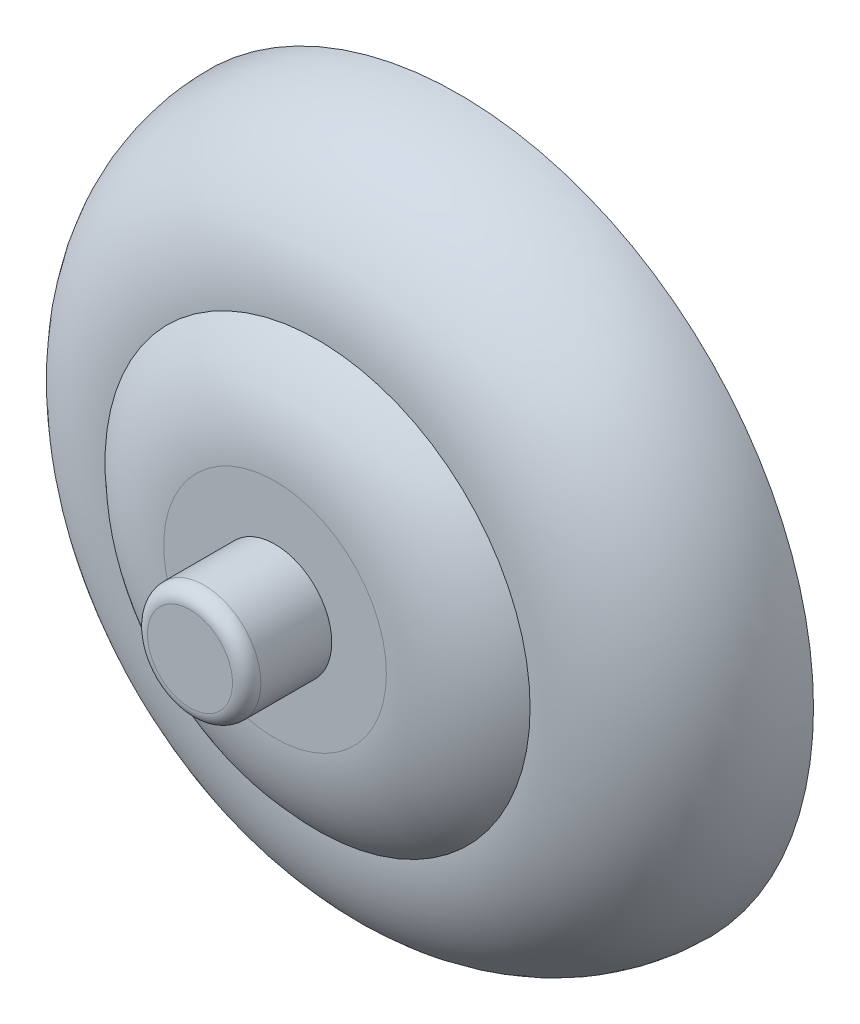
SolidWorks part; units mm, degrees
ref_plane "Plan de face" through (0, 0, 0) normal (0, 0, 1) x (1, 0, 0)
ref_plane "Plan de dessus" through (0, 0, 0) normal (0, 1, 0) x (1, 0, 0)
ref_plane "Plan de droite" through (0, 0, 0) normal (1, 0, 0) x (0, 0, -1)
sketch "Esquisse1" plane through (0, 0, 0) normal (0, 0, 1) x (1, 0, 0)
  circle A0 centre (0, 0) radius 25
  dimension "D1" = 50
extrude "Boss.-Extru.1" add sketch "Esquisse1" along normal blind 10
sketch "Esquisse2" plane through (0, 0, 10) normal (0, 0, 1) x (1, 0, 0)
  circle A0 centre (0, 0) radius 15
  dimension "D1" = 30
extrude "Boss.-Extru.2" add sketch "Esquisse2" along normal blind 3
sketch "Esquisse3" plane through (0, 0, 13) normal (0, 0, 1) x (1, 0, 0)
  circle A0 centre (0, 0) radius 4
  dimension "D1" = 8
extrude "Boss.-Extru.3" add sketch "Esquisse3" along normal blind 6
fillet "Congé1" radius 10 1 edges at (15, 0, 13)
fillet "Congé2" radius 1 1 edges at (4, 0, 19)
fillet "Congé3" radius 10 1 edges at (25, 0, 10)
